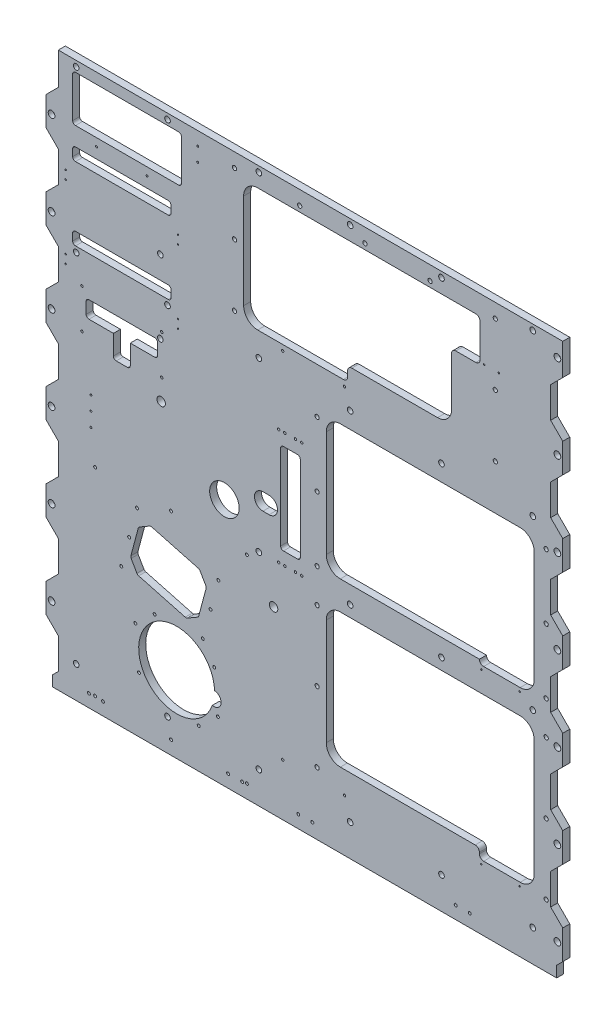
SolidWorks part; units mm, degrees
ref_plane "前视基准面" through (0, 0, 0) normal (0, 0, 1) x (1, 0, 0)
ref_plane "上视基准面" through (0, 0, 0) normal (0, 1, 0) x (1, 0, 0)
ref_plane "右视基准面" through (0, 0, 0) normal (1, 0, 0) x (0, 0, -1)
sketch "草图1" plane through (0, 0, 0) normal (0, 0, 1) x (1, 0, 0)
  line L1 (-924.5, 986.5) -> (924.5, 986.5)
  line L2 (-924.5, 986.5) -> (-924.5, -986.5)
  line L3 (-924.5, -986.5) -> (924.5, -986.5)
  line L4 (924.5, 986.5) -> (924.5, -986.5)
  line L5 (-924.5, 986.5) -> (924.5, -986.5) construction
  line L6 (-924.5, -986.5) -> (924.5, 986.5) construction
  point P0 (0, 0)
  dimension "D1" = 1973
  dimension "D2" = 1849
base flange "基体-法兰1" sketch "草图1" thickness 25 reverse thickness direction no parameters "D1"=1
sketch "草图6" plane through (0, 0, 0) normal (0, 0, 1) x (1, 0, 0)
  line L0 (924.5, 874.5) -> (881.5, 831.5)
  line L1 (924.5, -986.5) -> (924.5, 986.5) construction
  line L2 (881.5, 831.5) -> (881.5, 721.5)
  line L3 (881.5, 721.5) -> (924.5, 678.5)
  line L4 (924.5, 574.5) -> (881.5, 531.5)
  line L5 (881.5, 531.5) -> (881.5, 421.5)
  line L6 (881.5, 421.5) -> (924.5, 378.5)
  line L7 (924.5, 274.5) -> (881.5, 231.5)
  line L8 (881.5, 231.5) -> (881.5, 121.5)
  line L9 (881.5, 121.5) -> (924.5, 78.5)
  line L10 (924.5, -25.5) -> (881.5, -68.5)
  line L11 (881.5, -68.5) -> (881.5, -178.5)
  line L12 (881.5, -178.5) -> (924.5, -221.5)
  line L13 (924.5, -325.5) -> (881.5, -368.5)
  line L14 (881.5, -368.5) -> (881.5, -478.5)
  line L15 (881.5, -478.5) -> (924.5, -521.5)
  line L16 (924.5, -625.5) -> (881.5, -668.5)
  line L17 (881.5, -668.5) -> (881.5, -778.5)
  line L18 (881.5, -778.5) -> (924.5, -821.5)
  line L19 (924.5, 986.5) -> (-924.5, 986.5) construction
  line L20 (924.5, -925.5) -> (903, -947)
  line L21 (903, -947) -> (903, -986.5)
  line L22 (-924.5, -986.5) -> (924.5, -986.5) construction
  line L23 (924.5, -925.5) -> (924.5, -986.5)
  line L24 (924.5, -986.5) -> (903, -986.5)
  line L25 (924.5, -821.5) -> (924.5, -625.5)
  line L26 (924.5, -521.5) -> (924.5, -325.5)
  line L27 (924.5, -221.5) -> (924.5, -25.5)
  line L28 (924.5, 78.5) -> (924.5, 274.5)
  line L29 (924.5, 378.5) -> (924.5, 574.5)
  line L30 (924.5, 678.5) -> (924.5, 874.5)
  dimension "D1" = 112
  dimension "D2" = 43
  dimension "D3" = 155
  dimension "D4" = 110
  dimension "D5" = 104
  dimension "D6" = 190
  dimension "D7" = 110
  dimension "D8" = 43
  dimension "D9" = 190
  dimension "D10" = 110
  dimension "D11" = 110
  dimension "D12" = 110
  dimension "D13" = 110
  dimension "D14" = 104
  dimension "D15" = 104
  dimension "D16" = 190
  dimension "D17" = 104
  dimension "D18" = 190
  dimension "D19" = 104
  dimension "D20" = 190
  dimension "D21" = 43
  dimension "D22" = 21.5
  dimension "D23" = 104
  dimension "D24" = 39.5
extrude "切除-拉伸2" cut sketch "草图6" against normal through all normal cut yes
sketch "草图8" plane through (0, 0, 0) normal (0, 0, 1) x (1, 0, 0)
  line L0 (924.5, 874.5) -> (924.5, 986.5) construction
  line L1 (924.5, 986.5) -> (-924.5, 986.5) construction
  circle A0 centre (905.5, 926.5) radius 12
  circle A1 centre (905.5, 626.5) radius 12
  circle A2 centre (905.5, 326.5) radius 12
  circle A3 centre (905.5, 26.5) radius 12
  circle A4 centre (905.5, -273.5) radius 12
  circle A5 centre (905.5, -573.5) radius 12
  circle A6 centre (905.5, -873.5) radius 12
  point P17 (924.5, 930.5)
  dimension "D1" = 19
  dimension "D2" = 24
  dimension "D3" = 24
  dimension "D4" = 24
  dimension "D5" = 24
  dimension "D6" = 24
  dimension "D7" = 24
  dimension "D8" = 24
  dimension "D9" = 60
  dimension "D10" = 300
  dimension "D11" = 300
  dimension "D12" = 300
  dimension "D13" = 300
  dimension "D15" = 300
  dimension "D14" = 300
extrude "切除-拉伸3" cut sketch "草图8" against normal blind 16 normal cut yes
sketch "草图10" plane through (0, 0, 0) normal (0, 0, 1) x (1, 0, 0)
  line L0 (-924.5, 986.5) -> (-924.5, -986.5) construction
  line L1 (924.5, 986.5) -> (-924.5, 986.5) construction
  circle A0 centre (-807, 966.5) radius 10
  circle A1 centre (-482, 966.5) radius 10
  circle A2 centre (-157, 966.5) radius 10
  circle A3 centre (168, 966.5) radius 10
  circle A4 centre (493, 966.5) radius 10
  circle A5 centre (818, 966.5) radius 10
  circle A6 centre (-807, 394.5) radius 10
  circle A7 centre (493, 394.5) radius 10
  circle A8 centre (818, 394.5) radius 10
  circle A9 centre (168, 394.5) radius 10
  circle A10 centre (-157, 394.5) radius 10
  circle A11 centre (-482, 394.5) radius 10
  circle A12 centre (818, -203.5) radius 10
  circle A14 centre (493, -203.5) radius 10
  circle A15 centre (-157, -203.5) radius 10
  circle A16 centre (168, -203.5) radius 10
  circle A18 centre (818, -873.5) radius 10
  circle A19 centre (-482, -873.5) radius 10
  circle A20 centre (-807, -873.5) radius 10
  circle A21 centre (-157, -873.5) radius 10
  circle A22 centre (168, -873.5) radius 10
  circle A23 centre (493, -873.5) radius 10
  dimension "D1" = 325
  dimension "D2" = 325
  dimension "D3" = 325
  dimension "D4" = 325
  dimension "D5" = 325
  dimension "D6" = 117.5
  dimension "D7" = 20
  dimension "D8" = 20
  dimension "D9" = 20
  dimension "D10" = 20
  dimension "D11" = 20
  dimension "D12" = 20
  dimension "D13" = 20
  dimension "D14" = 20
  dimension "D15" = 20
  dimension "D16" = 20
  dimension "D17" = 20
  dimension "D18" = 20
  dimension "D19" = 20
  dimension "D20" = 20
  dimension "D21" = 20
  dimension "D22" = 20
  dimension "D23" = 20
  dimension "D24" = 20
  dimension "D25" = 20
  dimension "D26" = 325
  dimension "D27" = 325
  dimension "D28" = 20
  dimension "D29" = 20
  dimension "D30" = 20
  dimension "D31" = 20
  dimension "D32" = 572
  dimension "D34" = 670
  dimension "D35" = 325
  dimension "D36" = 117.5
  dimension "D38" = 325
  dimension "D39" = 325
  dimension "D41" = 325
  dimension "D42" = 325
  dimension "D43" = 325
  dimension "D44" = 325
  dimension "D45" = 325
  dimension "D46" = 325
  dimension "D47" = 325
  dimension "D48" = 117.5
  dimension "D33" = 598
  dimension "D37" = 325
  dimension "D40" = 325
extrude "切除-拉伸5" cut sketch "草图10" against normal blind 16 normal cut yes
sketch "草图9" plane through (0, 0, 0) normal (0, 0, 1) x (1, 0, 0)
  circle A0 centre (905.5, 926.5) radius 7
  circle A1 centre (905.5, 626.5) radius 7
  circle A2 centre (905.5, 326.5) radius 7
  circle A3 centre (905.5, 26.5) radius 7
  circle A4 centre (905.5, -273.5) radius 7
  circle A5 centre (905.5, -573.5) radius 7
  circle A6 centre (905.5, -873.5) radius 7
  circle A14 centre (818, 966.5) radius 5.25
  circle A15 centre (493, 966.5) radius 5.25
  circle A16 centre (168, 966.5) radius 5.25
  circle A17 centre (-157, 966.5) radius 5.25
  circle A18 centre (-482, 966.5) radius 5.25
  circle A19 centre (-807, 966.5) radius 5.25
  circle A20 centre (-807, 394.5) radius 5.25
  circle A21 centre (-482, 394.5) radius 5.25
  circle A22 centre (-157, 394.5) radius 5.25
  circle A23 centre (168, 394.5) radius 5.25
  circle A24 centre (493, 394.5) radius 5.25
  circle A25 centre (818, 394.5) radius 5.25
  circle A26 centre (818, -203.5) radius 5.25
  circle A27 centre (493, -203.5) radius 5.25
  circle A28 centre (168, -203.5) radius 5.25
  circle A29 centre (-157, -203.5) radius 5.25
  circle A30 centre (-807, -873.5) radius 5.25
  circle A31 centre (-482, -873.5) radius 5.25
  circle A32 centre (-157, -873.5) radius 5.25
  circle A33 centre (168, -873.5) radius 5.25
  circle A34 centre (493, -873.5) radius 5.25
  circle A35 centre (818, -873.5) radius 5.25
  dimension "D1" = 14
  dimension "D2" = 14
  dimension "D3" = 14
  dimension "D4" = 14
  dimension "D5" = 14
  dimension "D6" = 14
  dimension "D7" = 14
  dimension "D15" = 10.5
  dimension "D16" = 10.5
  dimension "D17" = 10.5
  dimension "D18" = 10.5
  dimension "D19" = 10.5
  dimension "D20" = 10.5
  dimension "D21" = 10.5
  dimension "D22" = 10.5
  dimension "D23" = 10.5
  dimension "D24" = 10.5
  dimension "D25" = 10.5
  dimension "D26" = 10.5
  dimension "D27" = 10.5
  dimension "D28" = 10.5
  dimension "D29" = 10.5
  dimension "D30" = 10.5
  dimension "D31" = 10.5
  dimension "D32" = 10.5
  dimension "D33" = 10.5
  dimension "D34" = 10.5
  dimension "D35" = 10.5
  dimension "D36" = 10.5
extrude "切除-拉伸4" cut sketch "草图9" against normal through all normal cut yes
sketch "草图11" plane through (0, 0, 0) normal (0, 0, 1) x (1, 0, 0)
  line L0 (-644.5, -280.615) -> (-644.5, 1050.9989) construction
  line L1 (-924.5, 986.5) -> (-924.5, -986.5) construction
  line L2 (-517.5, 271.5) -> (-771.5, 271.5)
  line L3 (-819.5, 948.5) -> (-432.5, 948.5)
  line L4 (-819.5, 948.5) -> (-819.5, 784.5)
  line L5 (-819.5, 784.5) -> (-432.5, 784.5)
  line L6 (-432.5, 948.5) -> (-432.5, 784.5)
  line L7 (-819.5, 718.5) -> (-469.5, 718.5)
  line L8 (-819.5, 718.5) -> (-819.5, 673.5)
  line L9 (-819.5, 673.5) -> (-469.5, 673.5)
  line L10 (-469.5, 718.5) -> (-469.5, 673.5)
  line L11 (-819.5, 458.5) -> (-469.5, 458.5)
  line L12 (-819.5, 458.5) -> (-819.5, 413.5)
  line L13 (-819.5, 413.5) -> (-469.5, 413.5)
  line L14 (-469.5, 458.5) -> (-469.5, 413.5)
  line L15 (-771.5, 271.5) -> (-771.5, 211.5)
  line L16 (-771.5, 211.5) -> (-674.5, 211.5)
  line L17 (-674.5, 211.5) -> (-674.5, 131.5)
  line L18 (-674.5, 131.5) -> (-614.5, 131.5)
  line L19 (-614.5, 211.5) -> (-614.5, 131.5)
  line L20 (-517.5, 211.5) -> (-614.5, 211.5)
  line L21 (-517.5, 271.5) -> (-517.5, 211.5)
  line L22 (924.5, 986.5) -> (-924.5, 986.5) construction
  line L23 (-211, 916.5) -> (630, 916.5)
  line L24 (630, 916.5) -> (630, 766.5)
  line L25 (630, 766.5) -> (529, 766.5)
  line L26 (529, 766.5) -> (529, 528.5)
  line L27 (529, 528.5) -> (159, 528.5)
  line L28 (-211, 478.5) -> (-211, 916.5)
  line L29 (159, 528.5) -> (159, 478.5)
  line L30 (159, 478.5) -> (-211, 478.5)
  line L31 (83, -141.5) -> (628, -141.5)
  line L32 (83, 336.5) -> (823, 336.5)
  line L33 (83, 336.5) -> (83, -141.5)
  line L34 (628, -141.5) -> (628, -156.5)
  line L35 (823, 336.5) -> (823, -156.5)
  line L36 (83, -243.5) -> (823, -243.5)
  line L37 (83, -243.5) -> (83, -721.5)
  line L38 (628, -156.5) -> (823, -156.5)
  line L39 (823, -243.5) -> (823, -756.5)
  line L40 (83, -721.5) -> (628, -721.5)
  line L41 (628, -721.5) -> (628, -756.5)
  line L42 (628, -756.5) -> (823, -756.5)
  line L43 (-924.5, -986.5) -> (903, -986.5) construction
  line L44 (924.5, -925.5) -> (924.5, -821.5) construction
  line L45 (-449.5, -763.5) -> (-449.5, -280.615) construction
  line L46 (-79.5, 165.5) -> (-9.5, 165.5)
  line L47 (-79.5, 165.5) -> (-79.5, -156.5)
  line L48 (-79.5, -156.5) -> (-9.5, -156.5)
  line L49 (-9.5, 165.5) -> (-9.5, -156.5)
  line L50 (-142.5, -40.5) -> (-120.5, -40.5) construction
  line L51 (-142.5, -10.5) -> (-120.5, -10.5)
  line L52 (-142.5, -70.5) -> (-120.5, -70.5)
  line L53 (-634.6101, -713.5) -> (-251.5936, -713.5) construction
  line L54 (-286.0589, -757.2939) -> (-642.6336, -661.75) construction
  line L55 (-584.2881, -397.8591) -> (-147.8754, -514.7955) construction
  line L56 (-496.2324, -887.9078) -> (-388.5239, -485.934) construction
  line L57 (-771.1894, -662.5494) -> (-210.6051, -751.3372) construction
  line L58 (-457.3794, -347.6496) -> (-495.9438, -491.5738) construction
  line L59 (-334.3986, -371.6419) -> (-575.8801, -306.9371)
  line L60 (-575.8801, -306.9371) -> (-622.4675, -480.8038)
  line L61 (-622.4675, -480.8038) -> (-380.9861, -545.5085)
  line L62 (-334.3986, -371.6419) -> (-380.9861, -545.5085)
  circle A0 centre (-243.5, 936.5) radius 7.5
  circle A1 centre (-243.5, 716.5) radius 7.5
  circle A2 centre (-243.5, 496.5) radius 7.5
  circle A3 centre (-11.5, 936.5) radius 7.5
  circle A4 centre (220.5, 936.5) radius 7.5
  circle A5 centre (452.5, 936.5) radius 7.5
  circle A6 centre (684.5, 936.5) radius 7.5
  circle A7 centre (684.5, 716.5) radius 7.5
  circle A8 centre (684.5, 496.5) radius 7.5
  circle A9 centre (-374.5, 938.5) radius 3.4
  circle A10 centre (-374.5, 888.5) radius 3.4
  circle A11 centre (-734.5, 756.5) radius 3.4
  circle A12 centre (-554.5, 756.5) radius 3.4
  circle A13 centre (-507.5, 538.5) radius 10
  circle A14 centre (-507.5, 278.5) radius 10
  circle A15 centre (-844.5, 630.5) radius 2.55
  circle A16 centre (-844.5, 600.5) radius 2.55
  circle A17 centre (-844.5, 370.5) radius 2.55
  circle A18 centre (-844.5, 340.5) radius 2.55
  circle A19 centre (-444.5, 340.5) radius 2.55
  circle A20 centre (-444.5, 370.5) radius 2.55
  circle A21 centre (-444.5, 600.5) radius 2.55
  circle A22 centre (-444.5, 630.5) radius 2.55
  circle A23 centre (-786.5, 301.5) radius 4.25
  circle A24 centre (-786.5, 161.5) radius 4.25
  circle A25 centre (-502.5, 161.5) radius 4.25
  circle A26 centre (-502.5, 301.5) radius 4.25
  circle A27 centre (-504.5, 86.5) radius 15
  circle A28 centre (-754.5, -18.5) radius 3.4
  circle A29 centre (-754.5, -68.5) radius 3.4
  circle A30 centre (-754.5, -118.5) radius 3.4
  circle A31 centre (645, 775) radius 2.55
  circle A32 centre (697, 775) radius 2.55
  circle A33 centre (50.5, 316.5) radius 7.5
  circle A34 centre (865.5, 316.5) radius 7.5
  circle A35 centre (865.5, 86.5) radius 7.5
  circle A36 centre (865.5, -263.5) radius 7.5
  circle A37 centre (50.5, 86.5) radius 7.5
  circle A38 centre (50.5, -263.5) radius 7.5
  circle A39 centre (50.5, -143.5) radius 7.5
  circle A40 centre (50.5, -763.5) radius 7.5
  circle A41 centre (50.5, -513.5) radius 7.5
  circle A42 centre (865.5, -143.5) radius 7.5
  circle A43 centre (865.5, -763.5) radius 7.5
  circle A44 centre (865.5, -513.5) radius 7.5
  circle A45 centre (-72, 458.5) radius 4.25
  circle A46 centre (148, 458.5) radius 4.25
  circle A47 centre (635, -170) radius 2.55
  circle A48 centre (771, -170) radius 2.55
  circle A49 centre (635, -770) radius 2.55
  circle A50 centre (771, -770) radius 2.55
  circle A51 centre (593.5, -941.5) radius 5.15
  circle A52 centre (543.5, -941.5) radius 5.15
  circle A53 centre (-16.5, -941.5) radius 5.15
  circle A54 centre (33.5, -941.5) radius 5.15
  circle A55 centre (-266.5, -941.5) radius 5.15
  circle A56 centre (-216.5, -941.5) radius 5.15
  circle A58 centre (-761.5, -941.5) radius 5.15
  circle A59 centre (-711.5, -941.5) radius 5.15
  circle A61 centre (148, -801.5) radius 4.25
  circle A62 centre (-72, -801.5) radius 4.25
  circle A63 centre (-86.5, 209.5) radius 4.25
  circle A64 centre (-64.5, 209.5) radius 4.25
  circle A65 centre (-26.5, 209.5) radius 4.25
  circle A66 centre (-4.5, 209.5) radius 4.25
  circle A67 centre (-86.5, -200.5) radius 4.25
  circle A68 centre (-64.5, -200.5) radius 4.25
  circle A69 centre (-4.5, -200.5) radius 4.25
  circle A70 centre (-26.5, -200.5) radius 4.25
  arc A71 (-142.5, -10.5) -> (-142.5, -70.5) centre (-142.5, -40.5) ccw
  arc A72 (-120.5, -70.5) -> (-120.5, -10.5) centre (-120.5, -40.5) ccw
  circle A73 centre (-104.5, -346.5) radius 15
  arc A74 (-314.5543, -709.6704) -> (-322.3425, -758.8427) centre (-449.5, -713.5) ccw
  circle A75 centre (-739.5, -938.5) radius 5.15
  circle A76 centre (-469.5, -938.5) radius 5.15
  circle A77 centre (-199.5, -938.5) radius 5.15
  circle A78 centre (-739.5, -233.5) radius 5.15
  circle A79 centre (-469.5, -233.5) radius 5.15
  circle A80 centre (-199.5, -233.5) radius 5.15
  circle A81 centre (-279.5, -103.5) radius 52.5
  circle A82 centre (-527.9288, -581.1929) radius 5.15
  circle A83 centre (-596.2836, -643.1112) radius 5.15
  circle A84 centre (-583.5749, -788.8669) radius 5.15
  circle A85 centre (-371.0712, -845.8071) radius 5.15
  circle A86 centre (-287.1873, -725.9333) radius 5.15 construction
  circle A87 centre (-315.4251, -638.1331) radius 5.15
  arc A88 (-322.3425, -758.8427) -> (-314.5543, -709.6704) centre (-316.1621, -734.6187) ccw
  circle A89 centre (-590.6693, -284.8571) radius 5.15
  circle A90 centre (-300.8915, -362.5028) radius 5.15
  circle A91 centre (-356.5376, -570.1768) radius 5.15
  circle A92 centre (-646.3154, -492.5311) radius 5.15
  circle A93 centre (-328.7146, -466.3398) radius 5.15
  circle A94 centre (-618.4923, -388.6941) radius 5.15
  circle A95 centre (-302.7164, -783.8888) radius 5.15
  circle A96 centre (-611.8127, -701.0667) radius 5.15 construction
  point P23 (-644.5, 131.5)
  point P26 (-644.5, 271.5)
  point P202 (-131.5, -40.5)
  point P256 (-501.7268, -513.1562)
  point P257 (-455.1394, -339.2895)
  dimension "D19" = 401
  dimension "D20" = 928
  dimension "D21" = 220
  dimension "D22" = 220
  dimension "D23" = 232
  dimension "D24" = 232
  dimension "D25" = 232
  dimension "D26" = 15
  dimension "D27" = 15
  dimension "D28" = 15
  dimension "D29" = 15
  dimension "D30" = 15
  dimension "D31" = 15
  dimension "D32" = 15
  dimension "D33" = 15
  dimension "D34" = 15
  dimension "D44" = 6.8
  dimension "D45" = 6.8
  dimension "D46" = 48
  dimension "D47" = 50
  dimension "D48" = 131
  dimension "D49" = 180
  dimension "D50" = 6.8
  dimension "D52" = 135
  dimension "D53" = 260
  dimension "D54" = 20
  dimension "D55" = 20
  dimension "D56" = 137
  dimension "D57" = 126
  dimension "D58" = 30
  dimension "D59" = 230
  dimension "D60" = 30
  dimension "D61" = 5.1
  dimension "D62" = 5.1
  dimension "D63" = 5.1
  dimension "D64" = 5.1
  dimension "D65" = 400
  dimension "D66" = 39
  dimension "D67" = 140
  dimension "D68" = 284
  dimension "D69" = 8.5
  dimension "D70" = 8.5
  dimension "D71" = 45
  dimension "D72" = 140
  dimension "D73" = 30
  dimension "D74" = 180
  dimension "D75" = 50
  dimension "D76" = 50
  dimension "D77" = 110
  dimension "D78" = 6.8
  dimension "D79" = 6.8
  dimension "D80" = 6.8
  dimension "D81" = 52
  dimension "D82" = 15
  dimension "D84" = 5.1
  dimension "D85" = 5.1
  dimension "D91" = 294
  dimension "D92" = 32.5
  dimension "D93" = 15
  dimension "D94" = 815
  dimension "D95" = 620
  dimension "D96" = 15
  dimension "D97" = 15
  dimension "D98" = 15
  dimension "D99" = 15
  dimension "D100" = 15
  dimension "D101" = 15
  dimension "D102" = 15
  dimension "D103" = 15
  dimension "D104" = 15
  dimension "D105" = 15
  dimension "D106" = 15
  dimension "D108" = 230
  dimension "D109" = 230
  dimension "D110" = 120
  dimension "D111" = 250
  dimension "D112" = 250
  dimension "D113" = 20
  dimension "D115" = 220
  dimension "D116" = 8.5
  dimension "D117" = 8.5
  dimension "D122" = 28.5
  dimension "D123" = 5.1
  dimension "D124" = 5.1
  dimension "D125" = 136
  dimension "D127" = 5.1
  dimension "D128" = 5.1
  dimension "D130" = 50
  dimension "D131" = 10.3
  dimension "D132" = 10.3
  dimension "D133" = 45
  dimension "D134" = 331
  dimension "D136" = 50
  dimension "D137" = 50
  dimension "D138" = 50
  dimension "D139" = 510
  dimension "D140" = 200
  dimension "D141" = 445
  dimension "D143" = 45
  dimension "D144" = 10.3
  dimension "D145" = 10.3
  dimension "D146" = 10.3
  dimension "D147" = 10.3
  dimension "D148" = 10.3
  dimension "D149" = 10.3
  dimension "D153" = 45
  dimension "D154" = 45
  dimension "D155" = 38
  dimension "D156" = 8.5
  dimension "D157" = 8.5
  dimension "D159" = 220
  dimension "D160" = 22
  dimension "D161" = 22
  dimension "D162" = 38
  dimension "D163" = 195
  dimension "D166" = 7
  dimension "D167" = 777
  dimension "D168" = 44
  dimension "D169" = 8.5
  dimension "D170" = 8.5
  dimension "D171" = 8.5
  dimension "D172" = 8.5
  dimension "D173" = 8.5
  dimension "D174" = 8.5
  dimension "D175" = 8.5
  dimension "D176" = 8.5
  dimension "D177" = 410
  dimension "D179" = 250
  dimension "D181" = 30
  dimension "D183" = 30
  dimension "D184" = 146
  dimension "D185" = 100
  dimension "D186" = 270
  dimension "D188" = 270
  dimension "D189" = 270
  dimension "D191" = 225
  dimension "D192" = 10.3
  dimension "D193" = 10.3
  dimension "D194" = 10.3
  dimension "D195" = 10.3
  dimension "D196" = 10.3
  dimension "D197" = 10.3
  dimension "D198" = 705
  dimension "D201" = 105
  dimension "D202" = 130
  dimension "D203" = 190
  dimension "D204" = 220
  dimension "D205" = 30
  dimension "D206" = 320
  dimension "D207" = 107.5
  dimension "D208" = 107.5
  dimension "D209" = 220
  dimension "D210" = 10.3
  dimension "D211" = 10.3
  dimension "D212" = 10.3
  dimension "D214" = 25
  dimension "D219" = 145
  dimension "D220" = 145
  dimension "D221" = 155
  dimension "D222" = 155
  dimension "D223" = 215
  dimension "D224" = 215
  dimension "D225" = 10.3
  dimension "D226" = 10.3
  dimension "D227" = 10.3
  dimension "D228" = 10.3
  dimension "D229" = 30
  dimension "D230" = 10.3
  dimension "D231" = 320
  dimension "D1" = 280
  dimension "D2" = 175
  dimension "D3" = 212
  dimension "D4" = 38
  dimension "D5" = 164
  dimension "D6" = 175
  dimension "D7" = 175
  dimension "D8" = 66
  dimension "D9" = 45
  dimension "D10" = 215
  dimension "D11" = 45
  dimension "D12" = 175
  dimension "D13" = 175
  dimension "D14" = 142
  dimension "D15" = 60
  dimension "D16" = 80
  dimension "D17" = 60
  dimension "D18" = 254
  dimension "D35" = 50
  dimension "D36" = 841
  dimension "D37" = 238
  dimension "D38" = 50
  dimension "D39" = 32.5
  dimension "D40" = 101
  dimension "D41" = 370
  dimension "D42" = 438
  dimension "D43" = 70
  dimension "D51" = 230
  dimension "D83" = 141.5
  dimension "D86" = 740
  dimension "D87" = 740
  dimension "D88" = 478
  dimension "D89" = 102
  dimension "D90" = 142
  dimension "D107" = 478
  dimension "D114" = 65
  dimension "D118" = 35
  dimension "D119" = 195
  dimension "D120" = 195
  dimension "D121" = 15
  dimension "D126" = 52
  dimension "D129" = 48.5
  dimension "D158" = 65
  dimension "D164" = 445
  dimension "D165" = 70
  dimension "D178" = 322
  dimension "D180" = 45
  dimension "D182" = 22
  dimension "D187" = 1700
  dimension "D190" = 20
  dimension "D199" = 15
  dimension "D200" = 270
  dimension "D213" = 6
  dimension "D215" = 102.3
  dimension "D216" = 250
  dimension "D217" = 90
  dimension "D218" = 90
extrude "切除-拉伸6" cut sketch "草图11" against normal through all normal cut yes
fillet "圆角1" radius 10 18 edges at (-517.5, 271.5, -12.5) (-517.5, 211.5, -12.5) (-614.5, 131.5, -12.5) (-771.5, 271.5, -12.5) (-771.5, 211.5, -12.5) (-674.5, 131.5, -12.5) (-469.5, 413.5, -12.5) (-819.5, 413.5, -12.5) (-819.5, 458.5, -12.5) (-469.5, 458.5, -12.5) (-819.5, 673.5, -12.5) (-819.5, 718.5, -12.5) (-469.5, 673.5, -12.5) (-469.5, 718.5, -12.5) (-819.5, 784.5, -12.5) (-432.5, 784.5, -12.5) (-432.5, 948.5, -12.5) (-819.5, 948.5, -12.5)
fillet "圆角2" radius 50 3 edges at (529, 528.5, -12.5) (-211, 478.5, -12.5) (-211, 916.5, -12.5)
fillet "圆角3" radius 15 5 edges at (630, 916.5, -12.5) (630, 766.5, -12.5) (529, 766.5, -12.5) (159, 528.5, -12.5) (159, 478.5, -12.5)
fillet "圆角4" radius 50 8 edges at (823, -756.5, -12.5) (823, -243.5, -12.5) (83, -721.5, -12.5) (83, -243.5, -12.5) (83, -141.5, -12.5) (823, -156.5, -12.5) (823, 336.5, -12.5) (83, 336.5, -12.5)
fillet "圆角5" radius 15 3 edges at (628, -156.5, -12.5) (628, -756.5, -12.5) (628, -721.5, -12.5)
fillet "圆角6" radius 10 4 edges at (-79.5, -156.5, -12.5) (-9.5, -156.5, -12.5) (-9.5, 165.5, -12.5) (-79.5, 165.5, -12.5)
chamfer "倒角1" distance 35 angle 45 4 edges at (-575.8801, -306.9371, -12.5) (-622.4675, -480.8038, -12.5) (-380.9861, -545.5085, -12.5) (-334.3986, -371.6419, -12.5)
fillet "圆角7" radius 10 8 edges at (-542.0727, -315.9958, -12.5) (-584.9388, -340.7445, -12.5) (-613.4088, -446.9964, -12.5) (-588.6601, -489.8624, -12.5) (-414.7935, -536.4499, -12.5) (-371.9274, -511.7011, -12.5) (-343.4573, -405.4493, -12.5) (-368.206, -362.5832, -12.5)
sketch "草图12" plane through (0, 0, 0) normal (0, 0, 1) x (1, 0, 0)
  line L0 (-924.5, 986.5) -> (-870.5, 986.5)
  line L2 (924.5, 986.5) -> (-924.5, 986.5) construction
  line L3 (-870.5, 986.5) -> (-870.5, 871.5)
  line L4 (-870.5, 871.5) -> (-913.5, 828.5)
  line L5 (-913.5, 828.5) -> (-913.5, 724.5)
  line L6 (-913.5, 724.5) -> (-870.5, 681.5)
  line L7 (-870.5, 681.5) -> (-870.5, 571.5)
  line L8 (-924.5, 986.5) -> (-924.5, -986.5) construction
  line L9 (-870.5, 571.5) -> (-913.5, 528.5)
  line L10 (-913.5, 528.5) -> (-913.5, 424.5)
  line L11 (-913.5, 424.5) -> (-870.5, 381.5)
  line L12 (-870.5, 381.5) -> (-870.5, 271.5)
  line L13 (-870.5, 271.5) -> (-913.5, 228.5)
  line L14 (-913.5, 228.5) -> (-913.5, 124.5)
  line L15 (-913.5, 124.5) -> (-870.5, 81.5)
  line L16 (-870.5, 81.5) -> (-870.5, -28.5)
  line L17 (-870.5, -28.5) -> (-913.5, -71.5)
  line L18 (-913.5, -71.5) -> (-913.5, -175.5)
  line L19 (-913.5, -175.5) -> (-870.5, -218.5)
  line L20 (-870.5, -218.5) -> (-870.5, -328.5)
  line L21 (-870.5, -328.5) -> (-913.5, -371.5)
  line L22 (-913.5, -371.5) -> (-913.5, -475.5)
  line L23 (-913.5, -475.5) -> (-870.5, -518.5)
  line L24 (-870.5, -518.5) -> (-870.5, -628.5)
  line L25 (-870.5, -628.5) -> (-913.5, -671.5)
  line L27 (-913.5, -671.5) -> (-913.5, -775.5)
  line L28 (-913.5, -775.5) -> (-870.5, -818.5)
  line L29 (-870.5, -818.5) -> (-870.5, -928.5)
  line L31 (-870.5, -928.5) -> (-892, -950)
  line L32 (-892, -950) -> (-892, -986.5)
  line L33 (-924.5, -986.5) -> (903, -986.5) construction
  line L34 (-892, -986.5) -> (-924.5, -986.5)
  line L35 (-924.5, -986.5) -> (-924.5, 986.5)
  dimension "D1" = 115
  dimension "D2" = 104
  dimension "D3" = 190
  dimension "D4" = 43
  dimension "D5" = 43
  dimension "D6" = 43
  dimension "D7" = 11
  dimension "D8" = 110
  dimension "D9" = 190
  dimension "D10" = 104
  dimension "D11" = 43
  dimension "D12" = 110
  dimension "D13" = 190
  dimension "D14" = 104
  dimension "D15" = 43
  dimension "D16" = 110
  dimension "D17" = 190
  dimension "D18" = 104
  dimension "D19" = 43
  dimension "D20" = 110
  dimension "D21" = 190
  dimension "D22" = 104
  dimension "D23" = 43
  dimension "D24" = 110
  dimension "D25" = 190
  dimension "D26" = 104
  dimension "D27" = 43
  dimension "D28" = 110
  dimension "D29" = 21.5
  dimension "D30" = 21.5
extrude "切除-拉伸7" cut sketch "草图12" against normal through all normal cut yes
sketch "草图13" plane through (0, 0, 0) normal (0, 0, 1) x (1, 0, 0)
  line L0 (-913.5, 724.5) -> (-913.5, 828.5) construction
  line L1 (924.5, 986.5) -> (-870.5, 986.5) construction
  circle A0 centre (-894.5, 776.5) radius 7
  circle A1 centre (-894.5, 476.5) radius 7
  circle A2 centre (-894.5, 176.5) radius 7
  circle A3 centre (-894.5, -123.5) radius 7
  circle A4 centre (-894.5, -423.5) radius 7
  circle A5 centre (-894.5, -723.5) radius 7
  dimension "D1" = 19
  dimension "D2" = 14
  dimension "D5" = 14
  dimension "D6" = 300
  dimension "D7" = 14
  dimension "D8" = 300
  dimension "D9" = 14
  dimension "D10" = 300
  dimension "D11" = 14
  dimension "D12" = 300
  dimension "D13" = 14
  dimension "D3" = 210
  dimension "D4" = 300
extrude "切除-拉伸8" cut sketch "草图13" against normal through all normal cut yes
sketch "草图14" plane through (0, 0, 0) normal (0, 0, 1) x (1, 0, 0)
  circle A0 centre (-894.5, 776.5) radius 12
  circle A1 centre (-894.5, 476.5) radius 12
  circle A2 centre (-894.5, 176.5) radius 12
  circle A3 centre (-894.5, -123.5) radius 12
  circle A4 centre (-894.5, -423.5) radius 12
  circle A5 centre (-894.5, -723.5) radius 12
  dimension "D1" = 24
  dimension "D2" = 24
  dimension "D3" = 24
  dimension "D4" = 24
  dimension "D5" = 24
  dimension "D6" = 24
extrude "切除-拉伸9" cut sketch "草图14" against normal blind 16
sketch "折弯-线1" [suppressed] plane through (0, 0, 0) normal (0, 1, 0) x (1, 0, 0)
sketch "边界框1" [suppressed] plane through (0, 0, 0) normal (0, 1, 0) x (1, 0, 0)
sheet metal parameters "钣金6" thickness 25 parameters "D1"=1
flat pattern "平板型式6" [suppressed]
sketch "折弯-线2" plane through (0, 0, 0) normal (0, 1, 0) x (1, 0, 0)
sketch "边界框2" [suppressed] plane through (0, 0, 0) normal (0, 1, 0) x (1, 0, 0)
sheet metal parameters "钣金7" thickness 25 parameters "D1"=1
flat pattern "平板型式6"
sketch "折弯-线2" plane through (0, 0, 0) normal (0, 1, 0) x (1, 0, 0)
sketch "边界框2" [suppressed] plane through (0, 0, 0) normal (0, 1, 0) x (1, 0, 0)
sheet metal parameters "钣金8" thickness 25 parameters "D1"=1
flat pattern "平板型式6"
sketch "折弯-线2" plane through (0, 0, 0) normal (0, 1, 0) x (1, 0, 0)
sketch "边界框2" [suppressed] plane through (0, 0, 0) normal (0, 1, 0) x (1, 0, 0)
sheet metal parameters "钣金9" thickness 25 parameters "D1"=1
flat pattern "平板型式6"
sketch "折弯-线2" plane through (0, 0, 0) normal (0, 1, 0) x (1, 0, 0)
sketch "边界框2" [suppressed] plane through (0, 0, 0) normal (0, 1, 0) x (1, 0, 0)
sheet metal parameters "钣金10" thickness 25 parameters "D1"=1
flat pattern "平板型式6"
sketch "折弯-线2" plane through (0, 0, 0) normal (0, 1, 0) x (1, 0, 0)
sketch "边界框2" [suppressed] plane through (0, 0, 0) normal (0, 1, 0) x (1, 0, 0)
sheet metal parameters "钣金11" thickness 25 parameters "D1"=1
flat pattern "平板型式6"
sketch "折弯-线2" plane through (0, 0, 0) normal (0, 1, 0) x (1, 0, 0)
sketch "边界框2" [suppressed] plane through (0, 0, 0) normal (0, 1, 0) x (1, 0, 0)
sheet metal parameters "钣金12" thickness 25 parameters "D1"=1
flat pattern "平板型式6"
sketch "折弯-线2" plane through (0, 0, 0) normal (0, 1, 0) x (1, 0, 0)
sketch "边界框2" [suppressed] plane through (0, 0, 0) normal (0, 1, 0) x (1, 0, 0)
sheet metal parameters "钣金13" thickness 25 parameters "D1"=1
flat pattern "平板型式6"
sketch "折弯-线2" plane through (0, 0, 0) normal (0, 1, 0) x (1, 0, 0)
sketch "边界框2" [suppressed] plane through (0, 0, 0) normal (0, 1, 0) x (1, 0, 0)
sheet metal parameters "钣金14" thickness 25 parameters "D1"=1
flat pattern "平板型式6"
sketch "折弯-线2" plane through (0, 0, 0) normal (0, 1, 0) x (1, 0, 0)
sketch "边界框2" [suppressed] plane through (0, 0, 0) normal (0, 1, 0) x (1, 0, 0)
